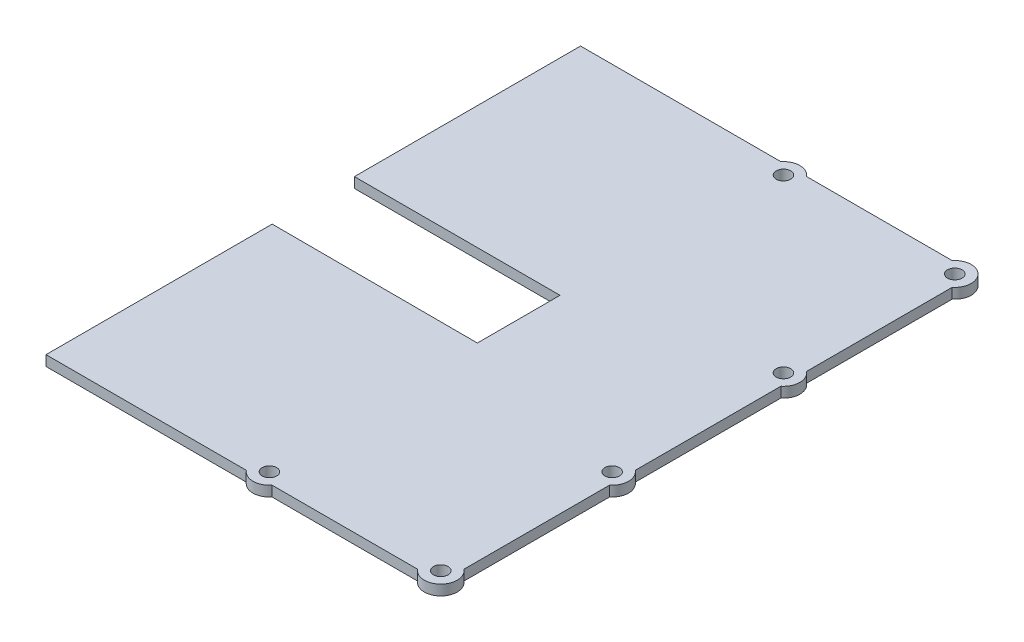
SolidWorks part; units mm, degrees
material "UHMW"
ref_plane "Front Plane" through (0, 0, 0) normal (0, 0, 1) x (1, 0, 0)
ref_plane "Top Plane" through (0, 0, 0) normal (0, 1, 0) x (1, 0, 0)
ref_plane "Right Plane" through (0, 0, 0) normal (1, 0, 0) x (0, 0, -1)
sketch "Sketch1" plane through (0, 0, 0) normal (0, 1, 0) x (1, 0, 0)
  circle A0 centre (65.8401, 3.175) radius 2.2479
  circle A1 centre (118.7568, 3.175) radius 2.2479
  circle A2 centre (118.7568, 56.0917) radius 2.2479
  circle A3 centre (118.7568, 109.0083) radius 2.2479
  circle A4 centre (118.7568, 161.925) radius 2.2479
  circle A5 centre (65.8401, 161.925) radius 2.2479
  line B0 (0, 165.1) -> (61.8745, 165.1)
  line B1 (0, 95.25) -> (0, 165.1)
  line B2 (0, 69.85) -> (0, 0)
  line B3 (61.8745, 0) -> (0, 0)
  line B4 (114.7912, 0) -> (69.8057, 0)
  line B5 (121.9318, 52.1261) -> (121.9318, 7.1406)
  line B6 (121.9318, 105.0428) -> (121.9318, 60.0572)
  line B7 (121.9318, 157.9594) -> (121.9318, 112.9739)
  line B8 (69.8057, 165.1) -> (114.7912, 165.1)
  line B9 (0, 95.25) -> (63.5, 95.25)
  line B10 (63.5, 95.25) -> (63.5, 69.7245)
  line B11 (63.5, 69.7245) -> (0, 69.85)
  arc B12 (69.8057, 165.1) -> (61.8745, 165.1) centre (65.8401, 161.925) ccw
  arc B13 (61.8745, 0) -> (69.8057, 0) centre (65.8401, 3.175) ccw
  arc B14 (114.7912, 0) -> (121.9318, 7.1406) centre (118.7568, 3.175) ccw
  arc B15 (121.9318, 52.1261) -> (121.9318, 60.0572) centre (118.7568, 56.0917) ccw
  arc B16 (121.9318, 105.0428) -> (121.9318, 112.9739) centre (118.7568, 109.0083) ccw
  arc B17 (121.9318, 157.9594) -> (114.7912, 165.1) centre (118.7568, 161.925) ccw
  dimension "D1" = 4.4958
sketch_block_instance "Block-bottomplate-1"
sketch_block "Block-bottomplate" parameters "D1"=63.5
extrude "Boss-Extrude1" add sketch "Sketch1" along normal blind 3.175
equation "\"Unit Measure\"= \"BoundingVolume\" / \"Thickness\"'in^2"
